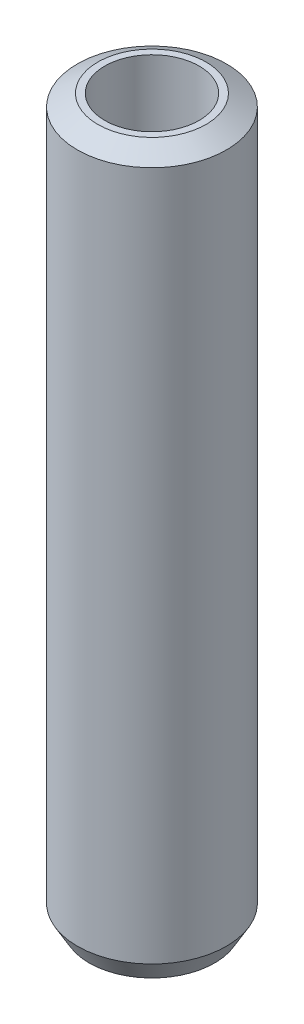
SolidWorks part; units mm, degrees
ref_plane "Front Plane" through (0, 0, 0) normal (0, 0, 1) x (1, 0, 0)
ref_plane "Top Plane" through (0, 0, 0) normal (0, 1, 0) x (1, 0, 0)
ref_plane "Right Plane" through (0, 0, 0) normal (1, 0, 0) x (0, 0, -1)
sketch "Sketch1" plane through (0, 0, 0) normal (0, 1, 0) x (1, 0, 0)
  circle A0 centre (0, 0) radius 22.5
  dimension "SHAFT_OD" = 45
extrude "Boss-Extrude1" add sketch "Sketch1" along normal blind 217.8032
sketch "Sketch2" plane through (0, 0, 0) normal (0, 1, 0) x (1, 0, 0)
  circle A0 centre (0, 0) radius 14.2385
  dimension "BORE_D" = 28.477
extrude "Cut-Extrude1" cut sketch "Sketch2" along normal through all
chamfer "Chamfer1" distance 3.5644 angle 60 2 edges at (0, 217.8032, 22.5) (0, 0, 22.5) first distance on face at (0, 217.8032, 22.5) first distance on face at (0, 0, 14.2385)
